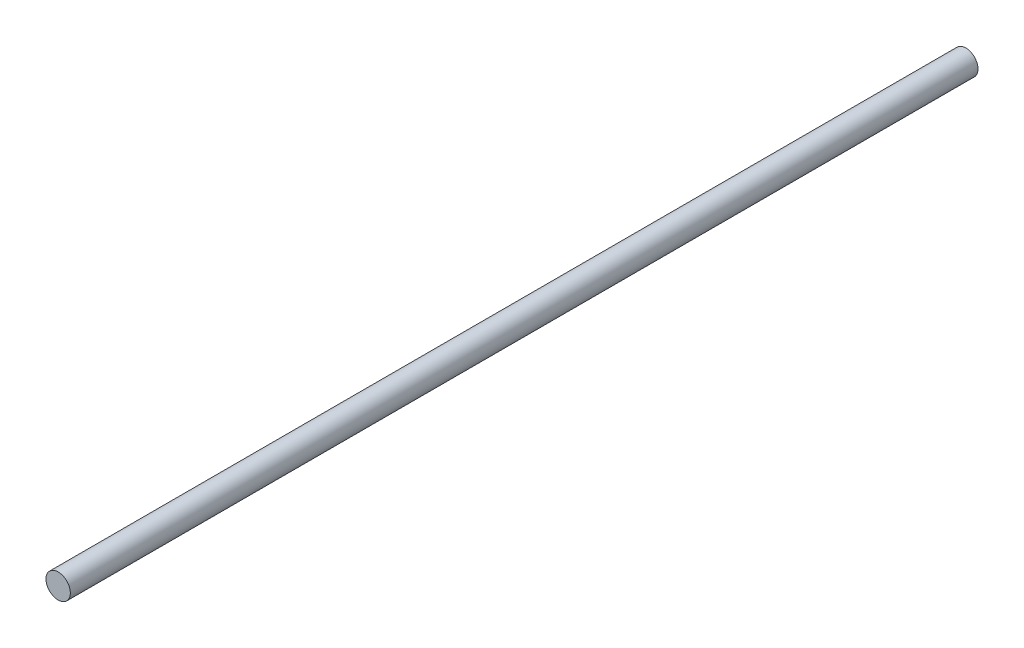
SolidWorks part; units mm, degrees
ref_plane "Front Plane" through (0, 0, 0) normal (0, 0, 1) x (1, 0, 0)
ref_plane "Top Plane" through (0, 0, 0) normal (0, 1, 0) x (1, 0, 0)
ref_plane "Right Plane" through (0, 0, 0) normal (1, 0, 0) x (0, 0, -1)
sketch "base" plane through (0, 0, 0) normal (0, 0, 1) x (1, 0, 0)
  circle A0 centre (0, 0) radius 51
  arc A1 (10.1018, 49.9895) -> (-10.1018, 49.9895) centre (0, 0) ccw construction
extrude "Boss-Extrude1" add sketch "base" along normal blind 2800 and the other way blind 1000
sketch "center" plane through (0, 0, 0) normal (0, 1, 0) x (1, 0, 0)
  line L0 (0, -2800) -> (0, 1000) construction
  line L1 (-51, -2800) -> (51, -2800) construction
  line L2 (51, 1000) -> (-51, 1000) construction
sketch "cutout" plane through (0, 0, 0) normal (0, 0, 1) x (1, 0, 0)
  circle A0 centre (0, 0) radius 49.5
  circle A1 centre (0, 0) radius 51 construction
  dimension "D1" = 1.5
extrude "Cut-Extrude1" cut sketch "cutout" against normal offset from surface 10 and the other way offset from surface 10 up to face at (51, 0, -1000) other way up to face at (51, 0, 2800)
